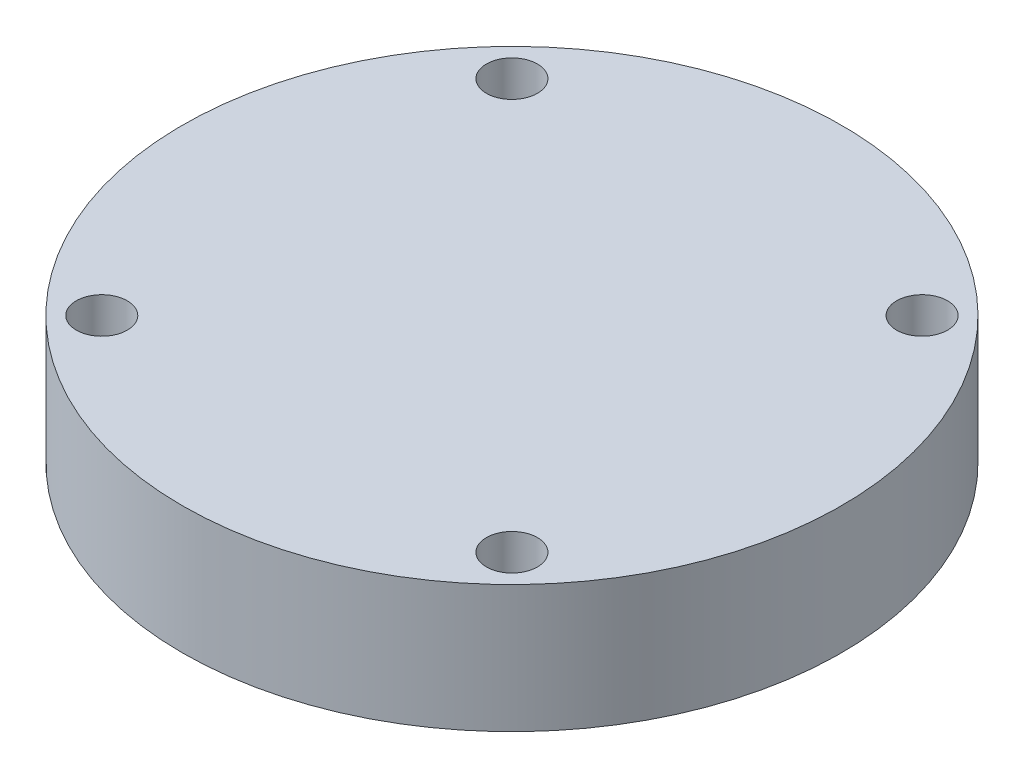
SolidWorks part; units mm, degrees
material "Copper"
ref_plane "Front Plane" through (0, 0, 0) normal (0, 0, 1) x (1, 0, 0)
ref_plane "Top Plane" through (0, 0, 0) normal (0, 1, 0) x (1, 0, 0)
ref_plane "Right Plane" through (0, 0, 0) normal (1, 0, 0) x (0, 0, -1)
ref_axis "Y Axis" through (0, 6.6675, 0) along (0, -1, 0)
sketch "outer" plane through (0, 0, 0) normal (0, 1, 0) x (1, 0, 0)
  circle A0 centre (0, 0) radius 19.05
  dimension "D1" = 38.1
extrude "Body" add sketch "outer" along normal blind 7.366
sketch "inner" plane through (0, 0, 0) normal (0, 1, 0) x (1, 0, 0)
  circle A0 centre (0, 0) radius 11.938
  dimension "D1" = 23.876
extrude "Pocket" cut sketch "inner" along normal blind 4.826
sketch "Screw Position" plane through (0, 0, 0) normal (0, 1, 0) x (1, 0, 0)
  point P0 (-11.8539, 11.8539)
  dimension "D1" = 16.764
hole_wizard "#4 Clearance Hole1" positions "Sketch7" profile "Sketch8" hole size "#4" standard "ANSI Inch" end condition through all
sketch "Sketch7" plane through (0, 7.366, 0) normal (0, 1, 0) x (1, 0, 0)
  point P0 (-11.8539, 11.8539)
sketch "Sketch8" plane through (-11.8539, 7.366, -11.8539) normal (1, 0, 0) x (0, 0, 1)
  line L0 (0, 0) -> (0, 7.366)
  line L1 (0, 7.366) -> (1.4732, 7.366)
  line L2 (1.4732, 7.366) -> (1.4732, 0)
  line L5 (1.4732, 0) -> (0, 0)
  line L11 (0, -6.35) -> (0, 107.95) construction
  dimension "Thru Hole Dia." = 2.9464
  dimension "Thru Hole Depth" = 7.366
pattern_circular "Screw Holes" count 4 over 360 about axis through (0, 6.6675, 0) along (0, -1, 0) of "#4 Clearance Hole1"
sketch "Post Sketch" plane through (0, 0, 0) normal (0, 1, 0) x (1, 0, 0)
  circle A0 centre (0, -5.334) radius 1
  circle A1 centre (5.334, -5.334) radius 1
  point P0 (0, -5.334)
  point P1 (5.334, -5.334)
  dimension "D3" = 2
  dimension "D4" = 2
  dimension "D1" = 5.334
  dimension "D2" = 7.5434
extrude "Post" add sketch "Post Sketch" against normal blind 4.826 from surface starting at face at (0, 4.826, 11.938)
pattern_circular "CirPattern1" count 4 over 360 about axis through (0, 6.6675, 0) along (0, -1, 0) of "Post"
equation "\"outer_d\"= 3 / 2in"
equation "\"top_h\"= 1 / 4in"
equation "\"screw_r\"= 0.66in"
equation "\"inner_d\"= 0.94in"
equation "\"inner_h\"= 150mil"
equation "\"D1@outer\" = \"outer_d\""
equation "\"D1@Body\"=\"top_h\" + \"inset_h\""
equation "\"D1@inner\"=\"inner_d\""
equation "\"D1@Pocket\"=\"inner_h\" + \"inset_h\""
equation "\"D1@Screw Position\"=\"screw_r\""
equation "\"post_r1\"= 0.21in"
equation "\"post_r2\"= \"post_r1\" * sqr ( 2 )"
equation "\"post_bottom_h\" = 0.04in"
equation "\"D1@Post Sketch\" = \"post_r1\""
equation "\"D2@Post Sketch\" = \"post_r2\""
equation "\"post_d\"= 2mm"
equation "\"D3@Post Sketch\"=\"post_d\""
equation "\"D4@Post Sketch\"=\"post_d\""
equation "\"D1@Post\" = \"inner_h\" + \"post_bottom_h\""
equation "\"inset_h\"= 0.04in"
